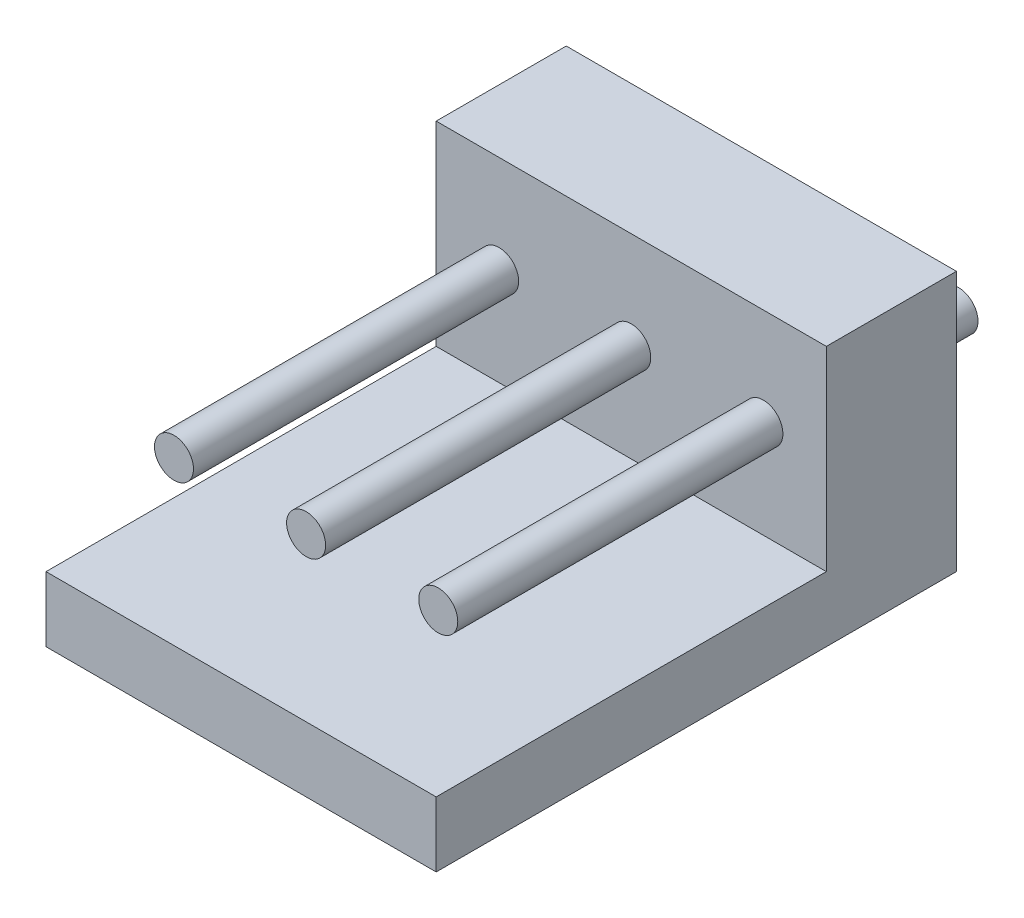
SolidWorks part; units mm, degrees
ref_plane "Спереди" through (0, 0, 0) normal (0, 0, 1) x (1, 0, 0)
ref_plane "Сверху" through (0, 0, 0) normal (0, 1, 0) x (1, 0, 0)
ref_plane "Справа" through (0, 0, 0) normal (1, 0, 0) x (0, 0, -1)
sketch "Эскиз1" plane through (0, 0, 0) normal (0, 0, 1) x (1, 0, 0)
  line L1 (0, 0) -> (15, 0)
  line L2 (0, 0) -> (0, 10)
  line L3 (0, 10) -> (15, 10)
  line L4 (15, 0) -> (15, 10)
  dimension "D1" = 15
  dimension "D2" = 10
extrude "Вытянуть1" add sketch "Эскиз1" along normal blind 5
sketch "Эскиз2" plane through (0, 0, 5) normal (0, 0, 1) x (1, 0, 0)
  line L1 (15, 0) -> (15, 10) construction
  line L2 (0, 0) -> (15, 0)
  line L3 (0, 0) -> (0, 2.5)
  line L4 (0, 2.5) -> (15, 2.5)
  line L7 (15, 0) -> (15, 2.5)
  dimension "D1" = 2.5
extrude "Вытянуть2" add sketch "Эскиз2" along normal blind 15
sketch "Эскиз3" plane through (0, 0, 5) normal (0, 0, 1) x (1, 0, 0)
  line L3 (7.5, 12.0229) -> (7.5, -0.8356) construction
  line L4 (0, 10) -> (0, 2.5) construction
  line L5 (15, 2.5) -> (15, 10) construction
  line L7 (7.5, 6.25) -> (17.66, 6.25) construction
  line L9 (15, 10) -> (0, 10) construction
  circle A0 centre (12.58, 6.25) radius 0.75
  circle A3 centre (2.42, 6.25) radius 0.75
  circle A4 centre (7.5, 6.25) radius 0.75
  dimension "D3" = 3.75
  dimension "D4" = 10.16
extrude "Вытянуть3" add sketch "Эскиз3" along normal blind 12.5 and the other way blind 7.5
